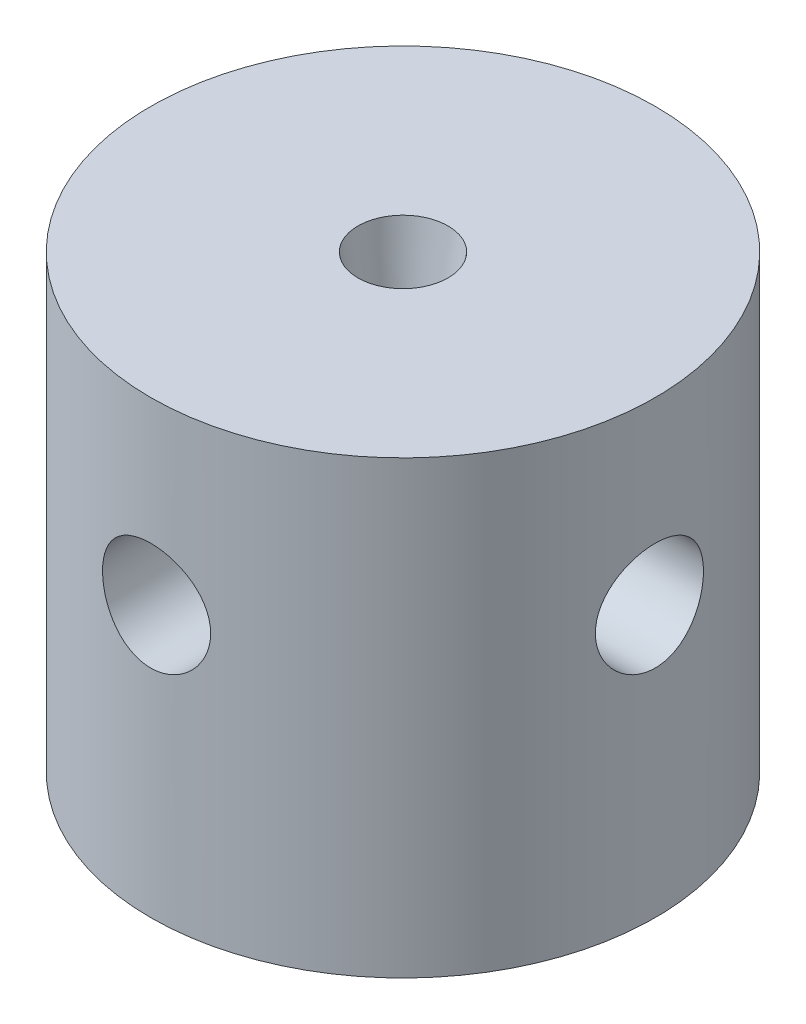
SolidWorks part; units mm, degrees
ref_plane "Front Plane" through (0, 0, 0) normal (0, 0, 1) x (1, 0, 0)
ref_plane "Top Plane" through (0, 0, 0) normal (0, 1, 0) x (1, 0, 0)
ref_plane "Right Plane" through (0, 0, 0) normal (1, 0, 0) x (0, 0, -1)
sketch "Sketch1" plane through (0, 0, 0) normal (0, 0, 1) x (1, 0, 0)
  line L0 (0, 20.7983) -> (0, -18.4168) construction
  line L1 (-12.7012, 0) -> (16.591, 0) construction
  line L2 (-1.5, 22.2735) -> (-1.5, -16.4653) construction
  line L3 (-1.5, 7.2676) -> (-1.5, -7.2676)
  line L4 (-1.5, -7.2676) -> (-14, -10.617)
  line L5 (-14, 23.4637) -> (-14, -15.7514) construction
  line L6 (-1.5, 7.2676) -> (-2.5, 14.383)
  line L7 (-2.5, 14.383) -> (-14, 14.383)
  line L8 (-14, 14.383) -> (-14, -10.617)
  point P10 (-1.5, 0)
  dimension "D1" = 25
  dimension "D2" = 14
  dimension "D3" = 8
  dimension "D4" = 1.5
  dimension "D5" = 2.5
  dimension "D6" = 75
revolve "Revolve1" add sketch "Sketch1" angle 360 about L0
ref_plane "Plane1" through (14, 0, 0) normal (1, 0, 0) x (0, 0, -1)
ref_axis "Axis1" through (0, -10.617, 0) along (0, 1, 0)
sketch "Sketch2" plane through (14, 0, 0) normal (1, 0, 0) x (0, 0, -1)
  line L0 (0, -10.617) -> (0, 14.383) construction
  line L2 (2.5, 14.383) -> (-2.5, 14.383) construction
  circle A0 centre (0, 4.383) radius 3
  dimension "D2" = 6
  dimension "D1" = 10
extrude "Cut-Extrude1" cut sketch "Sketch2" against normal blind 5
pattern_circular "CirPattern1" count 4 over 360 about axis through (0, -10.617, 0) along (0, 1, 0) of "Cut-Extrude1"
